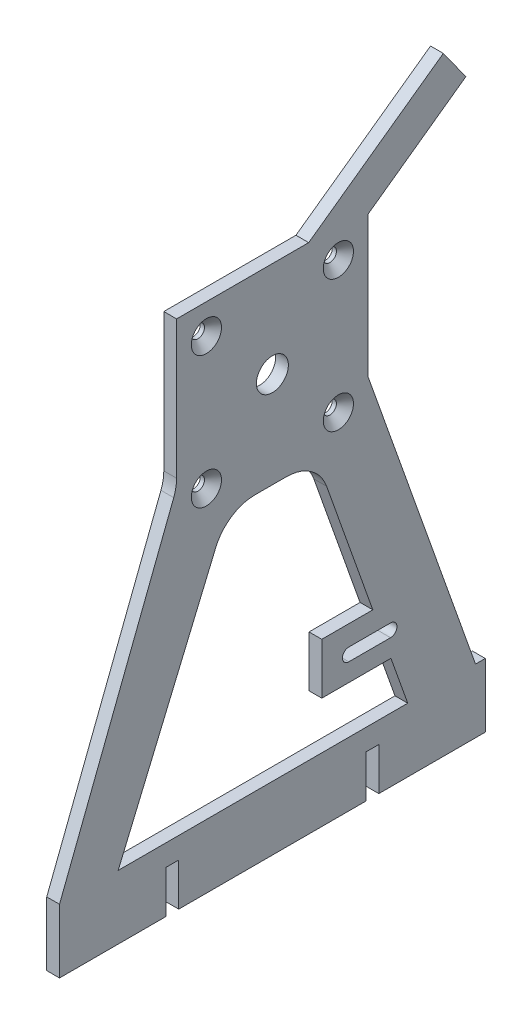
SolidWorks part; units mm, degrees
ref_plane "Front Plane" through (0, 0, 0) normal (0, 0, 1) x (1, 0, 0)
ref_plane "Top Plane" through (0, 0, 0) normal (0, 1, 0) x (1, 0, 0)
ref_plane "Right Plane" through (0, 0, 0) normal (1, 0, 0) x (0, 0, -1)
sketch "Sketch1" plane through (0, 0, 0) normal (1, 0, 0) x (0, 0, -1)
  line L21 (0, 15) -> (27.5, 86.0389)
  line L22 (27.5, 75.3197) -> (72.5, 75.3197)
  line L49 (50, 15) -> (50, 0) construction
  line L50 (50, 15) -> (50, 161.4393) construction
  line L51 (27.5, 75.3197) -> (27.5, 120.3197)
  line L52 (27.5, 120.3197) -> (72.5, 120.3197)
  line L53 (0, 0) -> (25, 0)
  line L54 (0, 0) -> (0, 15)
  line L56 (100, 0) -> (100, 15)
  line L65 (72.5, 75.3197) -> (72.5, 120.3197)
  line L66 (27.5, 75.3197) -> (72.5, 120.3197) construction
  line L67 (27.5, 120.3197) -> (72.5, 75.3197) construction
  line L75 (13.7779, 15) -> (39.2826, 75.3197)
  line L76 (60.3659, 75.3197) -> (73.5899, 38.0953)
  line L77 (72.5, 85.9722) -> (97.7129, 15)
  line L80 (97.7129, 15) -> (100, 15)
  line L88 (27.5, 86.0389) -> (39.2826, 75.3197)
  line L89 (60.3659, 75.3197) -> (72.5, 85.9722)
  line L92 (13.7779, 15) -> (50, 15)
  line L93 (50, 15) -> (81.7945, 15)
  line L94 (28, 0) -> (72, 0)
  line L96 (25, 0) -> (25, 10)
  line L97 (25, 10) -> (28, 10)
  line L98 (28, 0) -> (28, 10)
  line L100 (75, 0) -> (75, 10)
  line L101 (75, 10) -> (72, 10)
  line L102 (72, 0) -> (72, 10)
  line L103 (75, 0) -> (100, 0)
  line L105 (73.5899, 38.0953) -> (61.6052, 38.0953)
  line L106 (61.6052, 38.0953) -> (61.6052, 26.1111)
  line L107 (61.6052, 26.1111) -> (77.8473, 26.1111)
  line L108 (77.8473, 26.1111) -> (81.7945, 15)
  line L109 (58.5277, 120.3197) -> (90.1461, 143.0055)
  line L110 (90.1461, 143.0055) -> (95.4401, 135.6269)
  line L111 (95.4401, 135.6269) -> (68.3836, 116.2143)
  line L112 (68.3836, 116.2143) -> (58.5277, 120.3197)
  line L113 (67.9564, 31.8454) -> (77.7539, 31.8454) construction
  line L114 (67.9564, 33.3454) -> (77.7539, 33.3454)
  line L115 (67.9564, 30.3454) -> (77.7539, 30.3454)
  circle A0 centre (89.32, 136.7444) radius 1.5
  circle A6 centre (34.5, 82.3197) radius 1.55
  circle A7 centre (65.5, 82.3197) radius 1.55
  circle A8 centre (65.5, 113.3197) radius 1.55
  circle A9 centre (34.5, 113.3197) radius 1.55
  arc A11 (67.9564, 33.3454) -> (67.9564, 30.3454) centre (67.9564, 31.8454) ccw
  arc A12 (77.7539, 30.3454) -> (77.7539, 33.3454) centre (77.7539, 31.8454) ccw
  circle A13 centre (50, 97.8197) radius 3.75
  point P2 (50, 97.8197)
  point P36 (0, 0)
  point P43 (72.8551, 31.8454)
  point P57 (0, 0)
  point P58 (64.7416, 26.3742)
  point P59 (13.7779, 15)
  dimension "D2" = 3.1
  dimension "D3" = 3
  dimension "D4" = 2
  dimension "D5" = 2
  dimension "D6" = 3
  dimension "D19" = 7.5
  dimension "D10" = 3
  dimension "D8" = 10
  dimension "D7" = 15.5
  dimension "D9" = 15.5
  dimension "D11" = 10
  dimension "D12" = 3
  dimension "D13" = 25
  dimension "D14" = 25
  dimension "D15" = 45
  dimension "D16" = 45
  dimension "D17" = 100
  dimension "D18" = 15
  dimension "D20" = 15
extrude "Boss-Extrude2" add sketch "Sketch1" along normal blind 3 contours L51 L52 A0 | A6 | L52 L65 L22 L51 | L100 L101 L102 L94 L98 L97 L96 L53 L54 L21 L88 L75 L92 L93 L108 L107 L106 L105 L76 L89 L77 L80 L56 L103 | A9 | A8 | A7 | L110 L111 L112 L109 | L115 A12 L114 A11 | A13 region at (0, 129.7394, -78.9509)
chamfer "Chamfer1" distance 2 angle 45 4 edges at (3, 82.3197, -36.05) (3, 82.3197, -67.05) (3, 113.3197, -67.05) (3, 113.3197, -36.05)
fillet "Fillet2" radius 10 3 edges at (1.5, 75.3197, -60.3659) (1.5, 75.3197, -39.2826) (1.5, 86.0389, -27.5)
